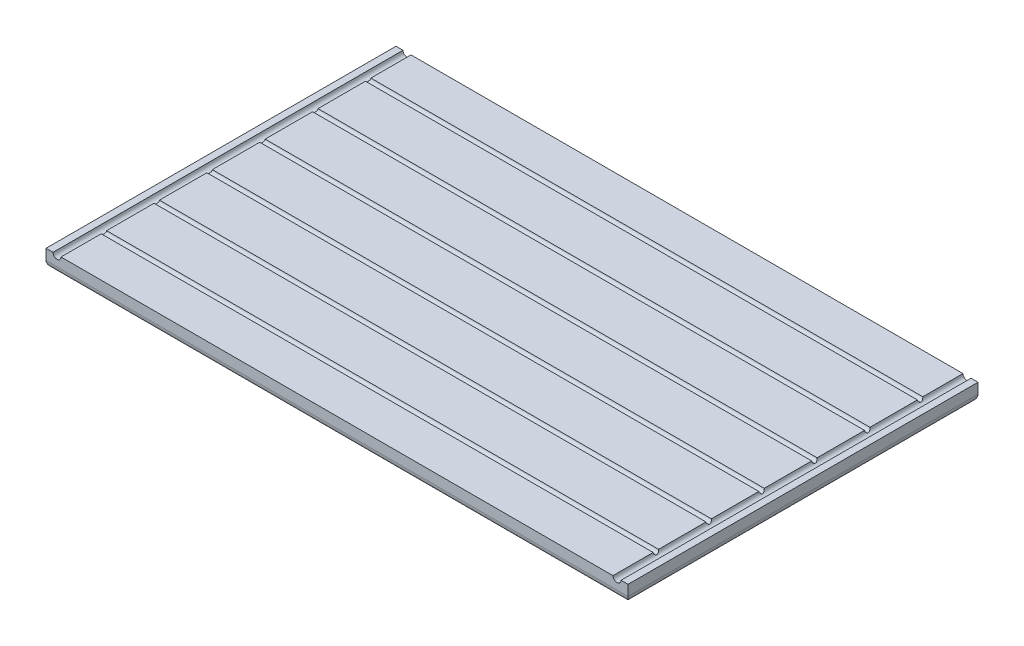
SolidWorks part; units mm, degrees
material "Polyurethane (PU) Foam"
ref_plane "Front Plane" through (0, 0, 0) normal (0, 0, 1) x (1, 0, 0)
ref_plane "Top Plane" through (0, 0, 0) normal (0, 1, 0) x (1, 0, 0)
ref_plane "Right Plane" through (0, 0, 0) normal (1, 0, 0) x (0, 0, -1)
sketch "Sketch1" plane through (0, 0, 0) normal (0, 0, 1) x (1, 0, 0)
  line L0 (11.45, 0) -> (1588.55, 0)
  line L1 (-11.45, 0) -> (-31.45, 0)
  line L2 (-31.45, 0) -> (-31.45, -50)
  line L3 (1631.45, 0) -> (1631.45, -50)
  line L4 (1611.45, 0) -> (1631.45, 0)
  line L5 (-31.45, -50) -> (1631.45, -50)
  arc A0 (-11.45, 0) -> (11.45, 0) centre (0, 0) ccw
  arc A1 (1588.55, 0) -> (1611.45, 0) centre (1600, 0) ccw
  dimension "D2" = 22.9
  dimension "D3" = 22.9
  dimension "D1" = 1600
  dimension "D4" = 50
  dimension "D5" = 20
  dimension "D6" = 20
  dimension "D7" = 50
extrude "Boss-Extrude1" add sketch "Sketch1" along normal blind 1000
sketch "Sketch2" plane through (1631.45, 0, 0) normal (1, 0, 0) x (0, 0, -1)
  line L0 (-1000, 0) -> (0, 0) construction
  line L1 (-1000, -50) -> (-1000, 0) construction
  line L2 (0, -50) -> (0, 0) construction
  circle A0 centre (-877.5, 0) radius 7.75
  circle A1 centre (-726.5, 0) radius 7.75
  circle A2 centre (-575.5, 0) radius 7.75
  circle A3 centre (-424.5, 0) radius 7.75
  circle A4 centre (-273.5, 0) radius 7.75
  circle A5 centre (-122.5, 0) radius 7.75
  dimension "D1" = 15.5
  dimension "D2" = 122.5
  dimension "D3" = 122.5
extrude "Cut-Extrude1" cut sketch "Sketch2" against normal through all
fillet "Fillet1" radius 20 4 edges at (-31.45, -50, 500) (800, -50, 1000) (1631.45, -50, 500) (800, -50, 0)
sketch "Sketch3" plane through (1631.45, 0, 0) normal (1, 0, 0) x (0, 0, -1)
  line L0 (-885.25, 0) -> (-869.75, 0)
  line L1 (-734.25, 0) -> (-718.75, 0)
  line L2 (-583.25, 0) -> (-567.75, 0)
  line L3 (-432.25, 0) -> (-416.75, 0)
  line L4 (-281.25, 0) -> (-265.75, 0)
  line L5 (-130.25, 0) -> (-114.75, 0)
  arc A0 (-885.25, 0) -> (-869.75, 0) centre (-877.5, 0) ccw
  arc A1 (-734.25, 0) -> (-718.75, 0) centre (-726.5, 0) ccw
  arc A2 (-583.25, 0) -> (-567.75, 0) centre (-575.5, 0) ccw
  arc A3 (-432.25, 0) -> (-416.75, 0) centre (-424.5, 0) ccw
  arc A4 (-281.25, 0) -> (-265.75, 0) centre (-273.5, 0) ccw
  arc A5 (-130.25, 0) -> (-114.75, 0) centre (-122.5, 0) ccw
extrude "Boss-Extrude2" add sketch "Sketch3" against normal up to surface (20 mm away) up to face at (1600, -4.1333, 500)
sketch "Sketch4" plane through (-31.45, 0, 0) normal (-1, 0, 0) x (0, 0, 1)
  line L0 (114.75, 0) -> (130.25, 0)
  line L1 (265.75, 0) -> (281.25, 0)
  line L2 (416.75, 0) -> (432.25, 0)
  line L3 (567.75, 0) -> (583.25, 0)
  line L4 (718.75, 0) -> (734.25, 0)
  line L5 (869.75, 0) -> (885.25, 0)
  arc A0 (114.75, 0) -> (130.25, 0) centre (122.5, 0) ccw
  arc A1 (265.75, 0) -> (281.25, 0) centre (273.5, 0) ccw
  arc A2 (416.75, 0) -> (432.25, 0) centre (424.5, 0) ccw
  arc A3 (567.75, 0) -> (583.25, 0) centre (575.5, 0) ccw
  arc A4 (718.75, 0) -> (734.25, 0) centre (726.5, 0) ccw
  arc A5 (869.75, 0) -> (885.25, 0) centre (877.5, 0) ccw
extrude "Boss-Extrude3" add sketch "Sketch4" against normal up to surface (20 mm away) up to face at (0, -4.1333, 500)
